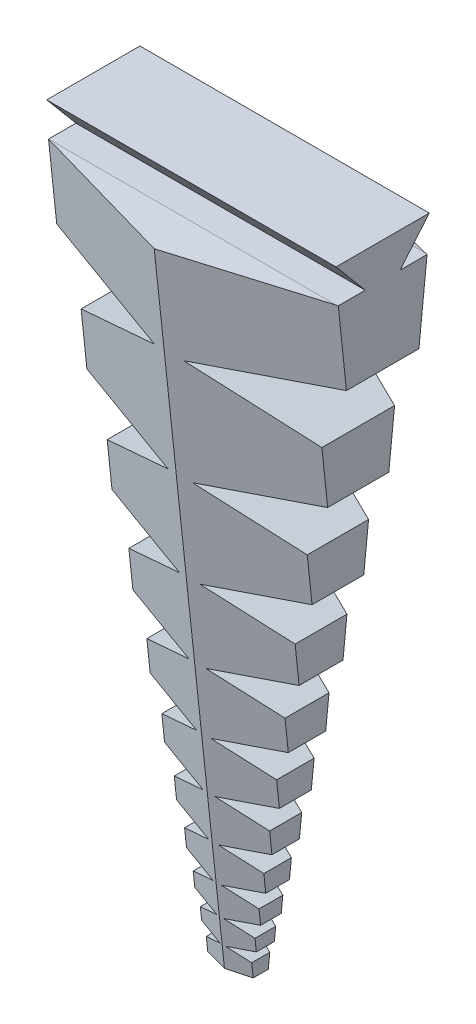
SolidWorks part; units mm, degrees
ref_plane "Front Plane" through (0, 0, 0) normal (0, 0, 1) x (1, 0, 0)
ref_plane "Top Plane" through (0, 0, 0) normal (0, 1, 0) x (1, 0, 0)
ref_plane "Right Plane" through (0, 0, 0) normal (1, 0, 0) x (0, 0, -1)
sketch "spiral_flat" plane through (0, 0, 0) normal (0, 0, 1) x (1, 0, 0)
  line L0 (3.2655, 0) -> (-3.2655, 0) construction
  line L1 (3.9293, 3.054) -> (-3.9293, 3.054) construction
  line L2 (4.728, 6.7288) -> (-4.728, 6.7288) construction
  line L3 (5.689, 11.1506) -> (-5.689, 11.1506) construction
  line L4 (6.8455, 16.4712) -> (-6.8455, 16.4712) construction
  line L5 (8.2369, 22.8733) -> (-8.2369, 22.8733) construction
  line L6 (9.9112, 30.5768) -> (-9.9112, 30.5768) construction
  line L7 (11.9259, 39.8461) -> (-11.9259, 39.8461) construction
  line L8 (14.35, 50.9996) -> (-14.35, 50.9996) construction
  line L9 (17.2669, 64.4202) -> (-17.2669, 64.4202) construction
  line L10 (20.7767, 80.5689) -> (-20.7767, 80.5689) construction
  line L11 (25, 100) -> (-25, 100) construction
  line L12 (0, -2.9617) -> (0, 103.8438) construction
  line L13 (3.2655, 0) -> (25, 100) construction
  line L14 (-3.2655, 0) -> (-25, 100) construction
  line L15 (0.3266, 0) -> (2.5, 100) construction
  line L16 (-0.3266, 0) -> (-2.5, 100) construction
  line L17 (-20.7767, 80.5689) -> (-20.7767, 100) construction
  line L18 (-17.2669, 64.4202) -> (-17.2669, 80.5689) construction
  line L19 (-14.35, 50.9996) -> (-14.35, 64.4202) construction
  line L20 (-11.9259, 39.8461) -> (-11.9259, 50.9996) construction
  line L21 (-9.9112, 30.5768) -> (-9.9112, 39.8461) construction
  line L22 (-8.2369, 22.8733) -> (-8.2369, 30.5768) construction
  line L23 (-6.8455, 16.4712) -> (-6.8455, 22.8733) construction
  line L24 (-5.689, 11.1506) -> (-5.689, 16.4712) construction
  line L25 (-4.728, 6.7288) -> (-4.728, 11.1506) construction
  line L26 (-3.9293, 3.054) -> (-3.9293, 6.7288) construction
  line L27 (-3.2655, 0) -> (-3.2655, 3.054) construction
  line L28 (20.7767, 80.5689) -> (20.7767, 100) construction
  line L29 (14.35, 50.9996) -> (14.35, 64.4202) construction
  line L30 (17.2669, 64.4202) -> (17.2669, 80.5689) construction
  line L31 (11.9259, 39.8461) -> (11.9259, 50.9996) construction
  line L32 (9.9112, 30.5768) -> (9.9112, 39.8461) construction
  line L33 (8.2369, 22.8733) -> (8.2369, 30.5768) construction
  line L34 (6.8455, 16.4712) -> (6.8455, 22.8733) construction
  line L35 (5.689, 11.1506) -> (5.689, 16.4712) construction
  line L36 (4.728, 6.7288) -> (4.728, 11.1506) construction
  line L37 (3.9293, 3.054) -> (3.9293, 6.7288) construction
  line L38 (3.2655, 0) -> (3.2655, 3.054) construction
  line L39 (-2.0777, 80.5689) -> (-17.2669, 75.0404) construction
  line L40 (-1.7267, 64.4202) -> (-17.2669, 67.1604) construction
  line L41 (-2.0777, 80.5689) -> (-20.7767, 83.866) construction
  line L42 (-1.7267, 64.4202) -> (-14.35, 59.8257) construction
  line L43 (-1.435, 50.9996) -> (-14.35, 53.2769) construction
  line L44 (-1.435, 50.9996) -> (-11.9259, 47.1812) construction
  line L45 (-1.1926, 39.8461) -> (-11.9259, 41.7387) construction
  line L46 (-1.1926, 39.8461) -> (-9.9112, 36.6728) construction
  line L47 (-0.9911, 30.5768) -> (-9.9112, 32.1496) construction
  line L48 (-0.9911, 30.5768) -> (-8.2369, 27.9395) construction
  line L49 (-0.8237, 22.8733) -> (-8.2369, 24.1805) construction
  line L50 (-0.8237, 22.8733) -> (-6.8455, 20.6816) construction
  line L51 (-0.6845, 16.4712) -> (-6.8455, 17.5576) construction
  line L52 (-0.6845, 16.4712) -> (-5.689, 14.6497) construction
  line L53 (-0.5689, 11.1506) -> (-5.689, 12.0534) construction
  line L54 (-0.5689, 11.1506) -> (-4.728, 9.6368) construction
  line L55 (-0.4728, 6.7288) -> (-4.728, 7.4791) construction
  line L56 (-0.4728, 6.7288) -> (-3.9293, 5.4708) construction
  line L57 (-0.3929, 3.054) -> (-3.9293, 3.6776) construction
  line L58 (-0.3929, 3.054) -> (-3.2655, 2.0085) construction
  line L59 (0.3929, 3.054) -> (3.2655, 2.0085) construction
  line L60 (0.3929, 3.054) -> (3.9293, 3.6776) construction
  line L61 (0.4728, 6.7288) -> (3.9293, 5.4708) construction
  line L62 (0.4728, 6.7288) -> (4.728, 7.4791) construction
  line L63 (0.5689, 11.1506) -> (4.728, 9.6368) construction
  line L64 (0.5689, 11.1506) -> (5.689, 12.0534) construction
  line L65 (0.6845, 16.4712) -> (5.689, 14.6497) construction
  line L66 (0.6845, 16.4712) -> (6.8455, 17.5576) construction
  line L67 (0.8237, 22.8733) -> (6.8455, 20.6816) construction
  line L68 (0.8237, 22.8733) -> (8.2369, 24.1805) construction
  line L69 (0.9911, 30.5768) -> (8.2369, 27.9395) construction
  line L70 (0.9911, 30.5768) -> (9.9112, 32.1496) construction
  line L71 (1.1926, 39.8461) -> (9.9112, 36.6728) construction
  line L72 (1.1926, 39.8461) -> (11.9259, 41.7387) construction
  line L73 (1.435, 50.9996) -> (11.9259, 47.1812) construction
  line L74 (1.435, 50.9996) -> (14.35, 53.2769) construction
  line L75 (1.7267, 64.4202) -> (14.35, 59.8257) construction
  line L76 (1.7267, 64.4202) -> (17.2669, 67.1604) construction
  line L77 (2.0777, 80.5689) -> (17.2669, 75.0404) construction
  line L78 (2.0777, 80.5689) -> (20.7767, 83.866) construction
  line L143 (-20.7767, 100) -> (-25, 100)
  line L144 (-25, 100) -> (-3.2655, 0)
  line L145 (-3.2655, 0) -> (-3.2655, 2.0085)
  line L146 (-0.3929, 3.054) -> (-3.9293, 3.6776)
  line L147 (-3.9293, 5.4708) -> (-0.4728, 6.7288)
  line L148 (-4.728, 7.4791) -> (-4.728, 9.6368)
  line L149 (-0.5689, 11.1506) -> (-5.689, 12.0534)
  line L150 (-5.689, 14.6497) -> (-0.6845, 16.4712)
  line L151 (-6.8455, 17.5576) -> (-6.8455, 20.6816)
  line L152 (-0.8237, 22.8733) -> (-8.2369, 24.1805)
  line L153 (-9.9112, 36.6728) -> (-1.1926, 39.8461)
  line L154 (-1.1926, 39.8461) -> (-11.9259, 41.7387)
  line L155 (-14.35, 59.8257) -> (-1.7267, 64.4202)
  line L156 (-1.7267, 64.4202) -> (-17.2669, 67.1604)
  line L157 (-17.2669, 75.0404) -> (-2.0777, 80.5689)
  line L158 (-20.7767, 83.866) -> (-20.7767, 100)
  line L159 (3.2655, 2.0085) -> (3.2655, 0)
  line L160 (0.3929, 3.054) -> (3.2655, 2.0085)
  line L161 (3.9293, 3.6776) -> (0.3929, 3.054)
  line L162 (3.9293, 5.4708) -> (3.9293, 3.6776)
  line L163 (0.4728, 6.7288) -> (3.9293, 5.4708)
  line L164 (4.728, 7.4791) -> (0.4728, 6.7288)
  line L165 (4.728, 9.6368) -> (4.728, 7.4791)
  line L166 (0.5689, 11.1506) -> (4.728, 9.6368)
  line L167 (5.689, 12.0534) -> (0.5689, 11.1506)
  line L168 (5.689, 14.6497) -> (5.689, 12.0534)
  line L169 (0.6845, 16.4712) -> (5.689, 14.6497)
  line L170 (6.8455, 17.5576) -> (0.6845, 16.4712)
  line L171 (6.8455, 20.6816) -> (6.8455, 17.5576)
  line L172 (0.8237, 22.8733) -> (6.8455, 20.6816)
  line L173 (8.2369, 24.1805) -> (0.8237, 22.8733)
  line L174 (8.2369, 27.9395) -> (8.2369, 24.1805)
  line L175 (0.9911, 30.5768) -> (8.2369, 27.9395)
  line L176 (9.9112, 32.1496) -> (0.9911, 30.5768)
  line L177 (9.9112, 36.6728) -> (9.9112, 32.1496)
  line L178 (1.1926, 39.8461) -> (9.9112, 36.6728)
  line L179 (11.9259, 41.7387) -> (1.1926, 39.8461)
  line L180 (11.9259, 47.1812) -> (11.9259, 41.7387)
  line L181 (1.435, 50.9996) -> (11.9259, 47.1812)
  line L182 (14.35, 53.2769) -> (1.435, 50.9996)
  line L183 (14.35, 59.8257) -> (14.35, 53.2769)
  line L184 (1.7267, 64.4202) -> (14.35, 59.8257)
  line L185 (17.2669, 67.1604) -> (1.7267, 64.4202)
  line L186 (17.2669, 75.0404) -> (17.2669, 67.1604)
  line L187 (2.0777, 80.5689) -> (17.2669, 75.0404)
  line L188 (20.7767, 83.866) -> (2.0777, 80.5689)
  line L189 (20.7767, 100) -> (20.7767, 83.866)
  line L190 (25, 100) -> (3.2655, 0)
  line L191 (20.7767, 100) -> (25, 100)
  line L192 (-20.7767, 83.866) -> (-2.0777, 80.5689)
  line L193 (-17.2669, 75.0404) -> (-17.2669, 67.1604)
  line L194 (-14.35, 59.8257) -> (-14.35, 53.2769)
  line L195 (-14.35, 53.2769) -> (-1.435, 50.9996)
  line L196 (-1.435, 50.9996) -> (-11.9259, 47.1812)
  line L197 (-11.9259, 47.1812) -> (-11.9259, 41.7387)
  line L198 (-9.9112, 36.6728) -> (-9.9112, 32.1496)
  line L199 (-9.9112, 32.1496) -> (-0.9911, 30.5768)
  line L200 (-0.9911, 30.5768) -> (-8.2369, 27.9395)
  line L201 (-8.2369, 27.9395) -> (-8.2369, 24.1805)
  line L202 (-6.8455, 20.6816) -> (-0.8237, 22.8733)
  line L203 (-6.8455, 17.5576) -> (-0.6845, 16.4712)
  line L204 (-5.689, 14.6497) -> (-5.689, 12.0534)
  line L205 (-0.5689, 11.1506) -> (-4.728, 9.6368)
  line L206 (-4.728, 7.4791) -> (-0.4728, 6.7288)
  line L207 (-3.9293, 5.4708) -> (-3.9293, 3.6776)
  line L208 (-0.3929, 3.054) -> (-3.2655, 2.0085)
  spline S0 degree 3 poles (0, 0) (0, 1.018) (0, 3.261) (0, 6.9778) (0, 11.4502) (0, 16.8317) (0, 23.3071) (0, 31.0987) (0, 40.4742) (0, 51.7553) (0, 65.3296) (0, 81.663) (0, 93.523) (0, 100) knots 0 0 0 0 0.03054 0.067288 0.111506 0.164712 0.228733 0.305768 0.398461 0.509996 0.644202 0.805689 1 1 1 1
  point P39 (0, 3.054)
  point P40 (0, 6.7288)
  point P41 (0, 11.1506)
  point P42 (0, 16.4712)
  point P43 (0, 22.8733)
  point P44 (0, 30.5768)
  point P45 (0, 39.8461)
  point P46 (0, 50.9996)
  point P47 (0, 64.4202)
  point P48 (0, 80.5689)
  point P49 (-0.3266, 0)
  point P50 (-0.3929, 3.054)
  point P51 (-0.4728, 6.7288)
  point P52 (-0.5689, 11.1506)
  point P53 (-0.6845, 16.4712)
  point P54 (-0.8237, 22.8733)
  point P55 (-0.9911, 30.5768)
  point P56 (-1.1926, 39.8461)
  point P57 (-1.435, 50.9996)
  point P58 (-1.7267, 64.4202)
  point P59 (-2.0777, 80.5689)
  point P60 (-2.5, 100)
  point P61 (0.3266, 0)
  point P62 (0.3929, 3.054)
  point P63 (0.4728, 6.7288)
  point P64 (0.5689, 11.1506)
  point P65 (0.6845, 16.4712)
  point P66 (0.8237, 22.8733)
  point P67 (0.9911, 30.5768)
  point P68 (1.1926, 39.8461)
  point P69 (1.435, 50.9996)
  point P70 (1.7267, 64.4202)
  point P71 (2.0777, 80.5689)
  point P72 (2.5, 100)
  dimension "D1" = 100
  dimension "D3" = 7.8586
  dimension "D2" = 6.531
  dimension "D4" = 9.456
  dimension "D5" = 11.3781
  dimension "D6" = 13.6909
  dimension "D7" = 16.4738
  dimension "D8" = 19.8224
  dimension "D9" = 23.8517
  dimension "D10" = 28.7
  dimension "D11" = 34.5338
  dimension "D12" = 41.5535
  dimension "D13" = 50
  dimension "D14" = 0.6531
  dimension "D15" = 0.7859
  dimension "D16" = 0.9456
  dimension "D17" = 1.1378
  dimension "D18" = 1.3691
  dimension "D19" = 1.6474
  dimension "D20" = 1.9822
  dimension "D21" = 2.3852
  dimension "D22" = 2.87
  dimension "D23" = 3.4534
  dimension "D24" = 4.1553
  dimension "D25" = 5
  dimension "D26" = 20
  dimension "D27" = 10
  dimension "D28" = 10
  dimension "D29" = 20
  dimension "D30" = 10
  dimension "D31" = 20
  dimension "D32" = 10
  dimension "D33" = 20
  dimension "D34" = 10
  dimension "D35" = 20
  dimension "D36" = 10
  dimension "D37" = 20
  dimension "D38" = 10
  dimension "D39" = 20
  dimension "D40" = 10
  dimension "D41" = 20
  dimension "D42" = 10
  dimension "D43" = 20
  dimension "D44" = 10
  dimension "D45" = 20
sketch "Sketch2" plane through (0, 0, 0) normal (0, 1, 0) x (1, 0, 0)
  line L0 (3.2655, 0) -> (-3.2384, 0) construction
  line L1 (0.0136, -1.9593) -> (0.0136, 1.9593) construction
  line L2 (3.2655, -1.9593) -> (3.2655, 1.9593) construction
  line L3 (-3.2384, -1.9593) -> (-3.2384, 1.9593) construction
  line L4 (3.2655, 1.9593) -> (-3.2384, 1.9593) construction
  line L5 (0.0136, 1.9593) -> (3.2655, 1.088) construction
  line L6 (3.2655, -1.9593) -> (-3.2384, -1.9593) construction
  line L7 (0.0136, -1.9593) -> (3.2655, -1.088) construction
  line L8 (0.0136, -1.9593) -> (-3.2384, -1.088) construction
  line L9 (0.0136, 1.9593) -> (-3.2384, 1.088) construction
  line L10 (0.0136, 1.9593) -> (-3.2384, 1.088)
  line L11 (-3.2384, 1.088) -> (-3.2384, -1.088)
  line L12 (-3.2384, -1.088) -> (0.0136, -1.9593)
  line L13 (0.0136, -1.9593) -> (3.2655, -1.088)
  line L14 (3.2655, -1.088) -> (3.2655, 1.088)
  line L15 (3.2655, 1.088) -> (0.0136, 1.9593)
  point P7 (0.0136, 0)
  dimension "D1" = 3.9186
  dimension "D2" = 15
ref_plane "Plane1" through (0, 100, 0) normal (0, 1, 0) x (1, 0, 0)
sketch "Sketch3" plane through (0, 100, 0) normal (0, 1, 0) x (1, 0, 0)
  line L2 (-0.1234, -12.5) -> (-0.1234, 12.5) construction
  line L5 (24.7531, 12.5) -> (-25, 12.5) construction
  line L6 (-0.1234, 12.5) -> (-25, 5.8343) construction
  line L7 (24.7531, -12.5) -> (-25, -12.5) construction
  line L8 (-0.1234, -12.5) -> (-25, -5.8343) construction
  line L9 (-0.1234, -12.5) -> (24.7531, -5.8343) construction
  line L10 (-0.1234, 12.5) -> (24.7531, 5.8343) construction
  line L12 (-25, -12.5) -> (-25, 12.5) construction
  line L15 (24.7531, -12.5) -> (24.7531, 12.5) construction
  line L16 (-0.1234, 12.5) -> (-25, 5.8343)
  line L17 (-25, 5.8343) -> (-25, -5.8343)
  line L18 (-25, -5.8343) -> (-0.1234, -12.5)
  line L19 (-0.1234, -12.5) -> (24.7531, -5.8343)
  line L20 (24.7531, -5.8343) -> (24.7531, 5.8343)
  line L21 (24.7531, 5.8343) -> (-0.1234, 12.5)
  point P8 (-0.1234, 0)
  dimension "D1" = 25
  dimension "D2" = 15
  dimension "D3" = 0.1234
  dimension "D4" = 24.8766
loft "Loft1" add profiles "Sketch2", "Sketch3" connector at (3.2655, 0, -1.0879) connector at (24.7531, 100, -5.8343)
extrude "Cut-Extrude2" cut sketch "spiral_flat" against normal through all both and the other way through all contours L192 L157 L193 L156 L155 L194 L195 L196 L197 L154 L153 L198 L199 L200 L201 L152 L202 L151 L203 L150 L204 L149 L205 L148 L206 L147 L207 L146 L208 L145 L144 L143 L158 | L188 L187 L186 L185 L184 L183 L182 L181 L180 L179 L178 L177 L176 L175 L174 L173 L172 L171 L170 L169 L168 L167 L166 L165 L164 L163 L162 L161 L160 L159 L190 L191 L189
ref_plane "Plane3" through (-20.7767, 0, 0) normal (-1, 0, 0) x (0, 0, 1)
sketch "Sketch6" plane through (-20.7767, 0, 0) normal (-1, 0, 0) x (0, 0, 1)
  line L0 (0, 100) -> (0, 83.866) construction
  line L1 (55, 100) -> (-55, 100) construction
  line L2 (-5.2594, 83.866) -> (5.2594, 83.866) construction
  line L3 (24.3259, 95) -> (-24.3259, 95) construction
  line L4 (2.5, 95) -> (6.6955, 100) construction
  line L5 (-2.5, 95) -> (-6.6955, 100) construction
  line L6 (2.5, 95) -> (6.6955, 100)
  line L7 (6.6955, 100) -> (6.966, 100)
  line L8 (6.966, 100) -> (5.2594, 83.866) construction
  line L9 (6.966, 100) -> (6.4371, 95)
  line L10 (6.4371, 95) -> (2.5, 95)
  line L11 (-2.5, 95) -> (-6.6955, 100)
  line L12 (-6.6955, 100) -> (-6.966, 100)
  line L13 (-6.966, 100) -> (-6.4371, 95)
  line L14 (-5.2594, 83.866) -> (-6.966, 100) construction
  line L15 (-6.4371, 95) -> (-2.5, 95)
  point P6 (0, 95)
  point P7 (-2.5, 95)
  point P10 (0, 95)
  point P11 (2.5, 95)
  dimension "D1" = 5
  dimension "D2" = 5
  dimension "D3" = 50
extrude "Cut-Extrude3" cut sketch "Sketch6" against normal through all and the other way through all contours L11 L12 L13 L15 | L10 L6 L7 L9
sketch "Sketch9" plane through (0, 0.3778, -3.5715) normal (0, 0.1052, -0.9945) x (-1, 0, 0)
  line L0 (-20.5436, 95.1501) -> (-20.5299, 100.178)
  line L1 (-20.5299, 100.178) -> (20.7767, 100.178)
  line L2 (20.7767, 100.178) -> (20.7767, 95.1501)
  line L3 (20.7767, 95.1501) -> (-20.5436, 95.1501)
extrude "Cut-Extrude5" cut sketch "Sketch9" against normal blind 10
sketch "Sketch10" plane through (0, 0.3778, 3.5715) normal (0, 0.1052, 0.9945) x (1, 0, 0)
  line L0 (20.5299, 100.178) -> (20.5436, 95.1501)
  line L1 (20.5436, 95.1501) -> (-20.7767, 95.1501)
  line L2 (-20.7767, 95.1501) -> (-20.7767, 100.178)
  line L3 (-20.7767, 100.178) -> (20.5299, 100.178)
extrude "Cut-Extrude6" cut sketch "Sketch10" against normal blind 10
sketch "Sketch11" plane through (0, 100, 0) normal (0, 1, 0) x (1, 0, 0)
  line L0 (-0.1234, -12.5) -> (20.5299, -6.966)
  line L1 (24.7531, -12.5) -> (-25, -12.5) construction
  line L2 (20.5299, -6.966) -> (-20.7767, -6.966)
  line L3 (-25, -5.8343) -> (-0.1234, -12.5) construction
  line L4 (-20.7767, 7.6627) -> (-20.7767, -7.6627) construction
  line L5 (-20.7767, -6.966) -> (-0.1234, -12.5)
  line L6 (-0.1234, 12.5) -> (-20.7767, 6.966)
  line L7 (-0.1234, 12.5) -> (-25, 5.8343) construction
  line L8 (20.5299, 6.966) -> (-20.7767, 6.966) construction
  line L9 (-20.7767, 6.966) -> (20.5299, 6.966)
  line L10 (20.5299, 6.966) -> (-0.1234, 12.5)
extrude "Cut-Extrude7" cut sketch "Sketch11" against normal blind 5
